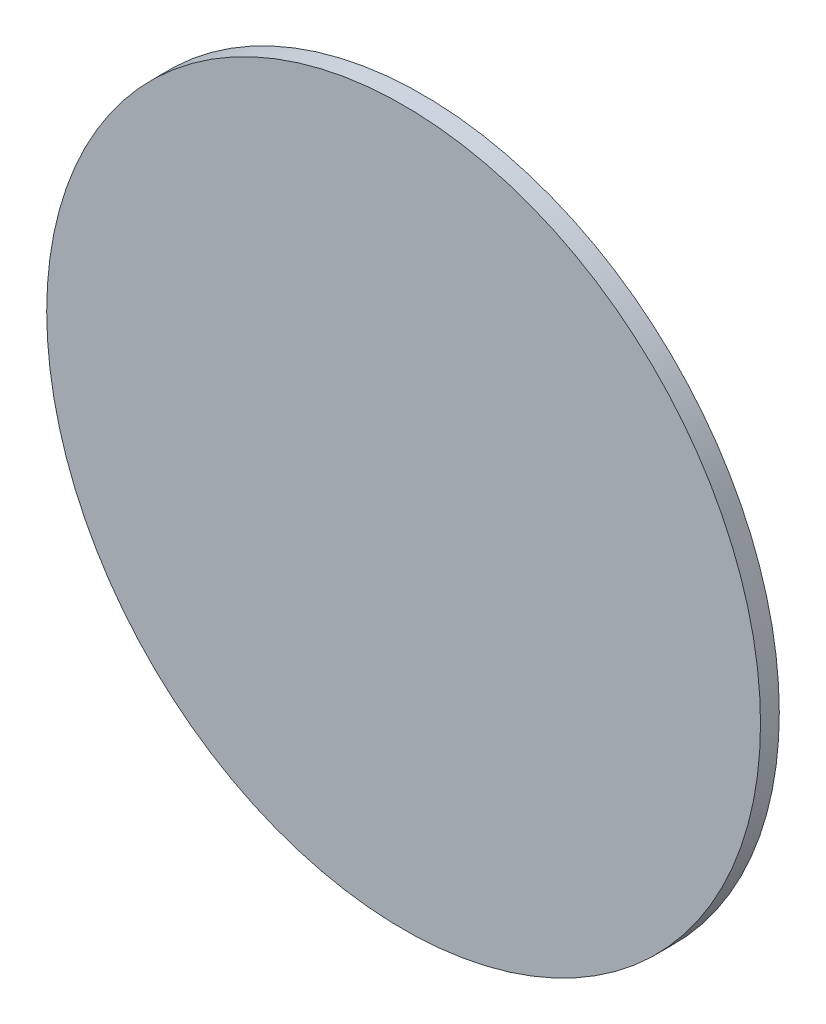
SolidWorks part; units mm, degrees
material "Acrylic (Medium-high impact)"
ref_plane "Front Plane" through (0, 0, 0) normal (0, 0, 1) x (1, 0, 0)
ref_plane "Top Plane" through (0, 0, 0) normal (0, 1, 0) x (1, 0, 0)
ref_plane "Right Plane" through (0, 0, 0) normal (1, 0, 0) x (0, 0, -1)
ref_axis "Axis1" through (0, 0, -12.1) along (0, 0, 1)
sketch "Sketch1" plane through (0, 0, 0) normal (0, 0, 1) x (1, 0, 0)
  circle A0 centre (0, 0) radius 38
  dimension "D1" = 76
extrude "Boss-Extrude1" add sketch "Sketch1" along normal blind 2
